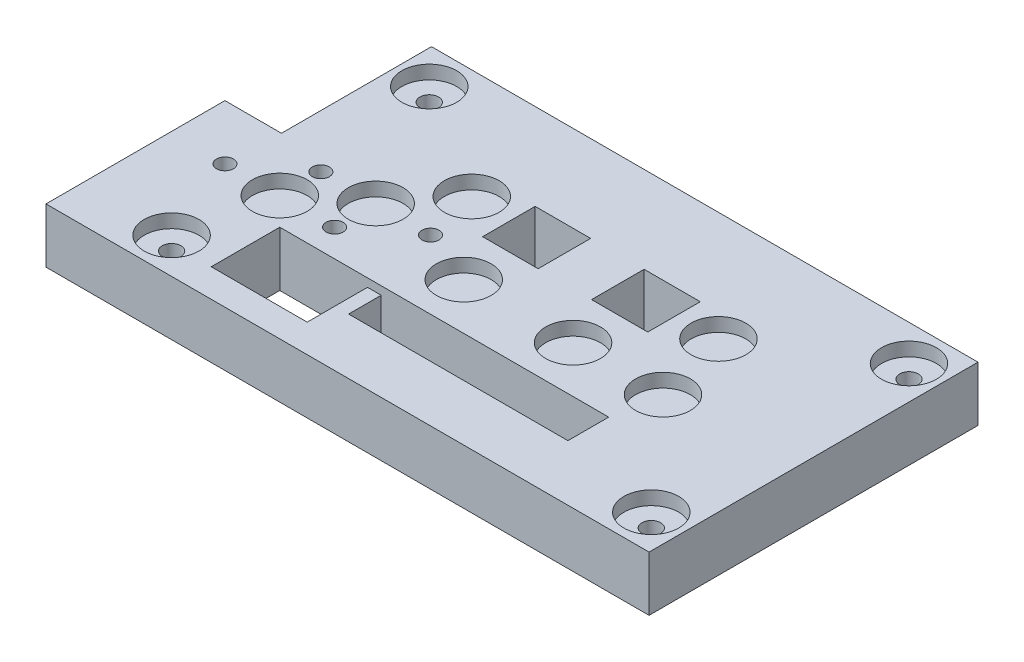
SolidWorks part; units mm, degrees
material "Plain Carbon Steel"
ref_plane "Front Plane" through (0, 0, 0) normal (0, 0, 1) x (1, 0, 0)
ref_plane "Top Plane" through (0, 0, 0) normal (0, 1, 0) x (1, 0, 0)
ref_plane "Right Plane" through (0, 0, 0) normal (1, 0, 0) x (0, 0, -1)
sketch "Sketch1" plane through (0, 0, 0) normal (0, 1, 0) x (1, 0, 0)
  line L1 (-110, -60) -> (110, -60)
  line L2 (-110, -60) -> (-110, 60)
  line L3 (-110, 60) -> (110, 60)
  line L4 (110, -60) -> (110, 60)
  line L5 (-110, -60) -> (110, 60) construction
  line L6 (-110, 60) -> (110, -60) construction
  point P0 (0, 0)
  dimension "D1" = 120
  dimension "D2" = 220
extrude "Boss-Extrude1" add sketch "Sketch1" against normal blind 20
sketch "Sketch2" plane through (0, 0, 0) normal (0, 1, 0) x (1, 0, 0)
  line L1 (-110, 60) -> (-89.3675, 60)
  line L2 (-110, 60) -> (-110, 5.27)
  line L3 (-110, 5.27) -> (-89.3675, 5.27)
  line L4 (-89.3675, 60) -> (-89.3675, 5.27)
  line L5 (-90, -14.72) -> (-89.3675, 5.27) construction
  line L10 (-70, 0.28) -> (-89.3675, 5.27) construction
  circle A0 centre (-90, -14.72) radius 3.1 construction
  circle A1 centre (-70, 0.28) radius 3.1 construction
  dimension "D1" = 20
extrude "Cut-Extrude1" cut sketch "Sketch2" against normal up to next
sketch "Sketch3" plane through (0, 0, 0) normal (0, 1, 0) x (1, 0, 0)
  line L6 (-20, 28.44) -> (-20, 9.28)
  line L7 (-20, 9.28) -> (0.25, 9.28)
  line L8 (0.25, 9.28) -> (0.25, 28.44)
  line L9 (19.75, 28.44) -> (19.75, 9.28)
  line L10 (19.75, 9.28) -> (40.25, 9.28)
  line L11 (40.25, 9.28) -> (40.25, 28.44)
  line L12 (-20, 28.44) -> (0.25, 28.44)
  line L14 (19.75, 28.44) -> (40.25, 28.44)
  line L15 (5.31, 28.5) -> (-15.06, 28.5) construction
  line L18 (40.25, 9.28) -> (40.25, 27.5) construction
  line L19 (19.75, 27.5) -> (19.75, 9.28) construction
  line L20 (19.75, 9.28) -> (40.25, 9.28) construction
  line L21 (0.25, 9.28) -> (0.25, 27.5) construction
  line L22 (-20, 9.28) -> (0.25, 9.28) construction
  line L23 (-20, 27.5) -> (-20, 9.28) construction
  dimension "D1" = 0.06
extrude "Cut-Extrude2" cut sketch "Sketch3" against normal up to next
sketch "Sketch4" plane through (0, 0, 0) normal (0, 1, 0) x (1, 0, 0)
  line L0 (-15.06, -39.66) -> (65.06, -39.66) construction
  line L1 (60, -24.72) -> (-20, -24.72)
  line L2 (60, -24.72) -> (60, -39.6)
  line L3 (60, -39.6) -> (-20, -39.6)
  line L4 (-20, -24.72) -> (-20, -39.6)
  dimension "D1" = 80
  dimension "D2" = 0.06
  dimension "D3" = 14.88
extrude "Cut-Extrude3" cut sketch "Sketch4" against normal up to next
sketch "Sketch8" plane through (0, 0, 0) normal (0, 1, 0) x (1, 0, 0)
  circle A0 centre (-70, 0.28) radius 3.1 construction
  circle A1 centre (-90, -14.72) radius 3.1
  circle A2 centre (-90, -14.72) radius 3.1
  circle A3 centre (-30, 0.28) radius 3.1
  circle A4 centre (-30, 0.28) radius 3.1
  circle A5 centre (-70, 0.28) radius 3.1
  circle A6 centre (-50, -14.72) radius 3.1 construction
  circle A7 centre (-50, -14.72) radius 3.1
  dimension "D1" = 0
  dimension "D2" = 0
extrude "Cut-Extrude4" cut sketch "Sketch8" against normal up to next
sketch "Sketch9" plane through (0, 0, 0) normal (0, 1, 0) x (1, 0, 0)
  line L0 (-20, -27.72) -> (-25, -27.72)
  line L1 (-20, -24.72) -> (-60, -24.72)
  line L2 (-20, -24.72) -> (-20, -27.72)
  line L3 (-25, -49.72) -> (-60, -49.72)
  line L4 (-60, -24.72) -> (-60, -49.72)
  line L5 (-25, -27.72) -> (-25, -49.72)
  dimension "D1" = 25
  dimension "D2" = 5
  dimension "D3" = 35
  dimension "D4" = 3
extrude "Cut-Extrude5" cut sketch "Sketch9" against normal up to next
sketch "Sketch10" plane through (0, 0, 0) normal (0, 1, 0) x (1, 0, 0)
  line L0 (-70, 0.28) -> (-50, 0.28) construction
  line L1 (-50, 0.28) -> (-50, -14.72) construction
  line L2 (-70, 0.28) -> (-70, -14.72) construction
  line L3 (-70, -14.72) -> (-50, -14.72) construction
  line L5 (110, 60) -> (-89.3675, 60) construction
  line L6 (110, 60) -> (-89.3675, 60) construction
  line L9 (-110, -60) -> (110, -60) construction
  line L11 (10.3163, 60) -> (10.3163, -60) construction
  line L12 (30, 9.28) -> (30, -24.72) construction
  line L13 (19.75, 9.28) -> (40.25, 9.28) construction
  line L14 (60, -24.72) -> (-60, -24.72) construction
  line L15 (-9.875, 9.28) -> (-9.875, -24.72) construction
  line L16 (-20, 9.28) -> (0.25, 9.28) construction
  circle A0 centre (-77.1837, 47) radius 10
  circle A1 centre (-34.6837, 20) radius 10
  circle A5 centre (97.8163, 47) radius 10
  circle A6 centre (30, -7.72) radius 10
  circle A7 centre (55.3163, 20) radius 10
  circle A8 centre (-9.875, -7.72) radius 10
  circle A9 centre (97.8163, -47) radius 10
  circle A10 centre (-50, 0.28) radius 10
  circle A11 centre (62.8163, -7.72) radius 10
  circle A12 centre (-70, -14.72) radius 10
  circle A13 centre (-77.1837, -47) radius 10
  point P59 (30, -7.72)
  point P61 (-9.875, -7.72)
  dimension "D1" = 20
  dimension "D4" = 90
  dimension "D2" = 175
  dimension "D3" = 13
  dimension "D5" = 13
  dimension "D6" = 35
  dimension "D7" = 40
extrude "Cut-Extrude6" cut sketch "Sketch10" against normal blind 5 and the other way through all
hole_wizard "M8 Tapped Hole1" positions "Sketch13" profile "Sketch12" tap size "M8" standard "ISO" end condition through all
sketch "Sketch13" plane through (0, -5, 0) normal (0, 1, 0) x (1, 0, 0)
  point P0 (-77.1837, 47)
  point P3 (97.8163, 47)
  point P6 (97.8163, -47)
  point P9 (-77.1837, -47)
sketch "Sketch12" plane through (-77.1837, -5, -47) normal (1, 0, 0) x (0, 0, 1)
  line L0 (0, 0) -> (0, 15)
  line L1 (0, 15) -> (3.4, 15)
  line L2 (3.4, 15) -> (3.4, 0)
  line L5 (3.4, 0) -> (0, 0)
  line L11 (0, -6.35) -> (0, 107.95) construction
  dimension "Thru Tap Drill Dia." = 6.8
  dimension "Thru Tap Drill Depth" = 15
cosmetic thread "Hole Thread1"
cosmetic thread "Hole Thread2"
cosmetic thread "Hole Thread3"
cosmetic thread "Hole Thread4"
